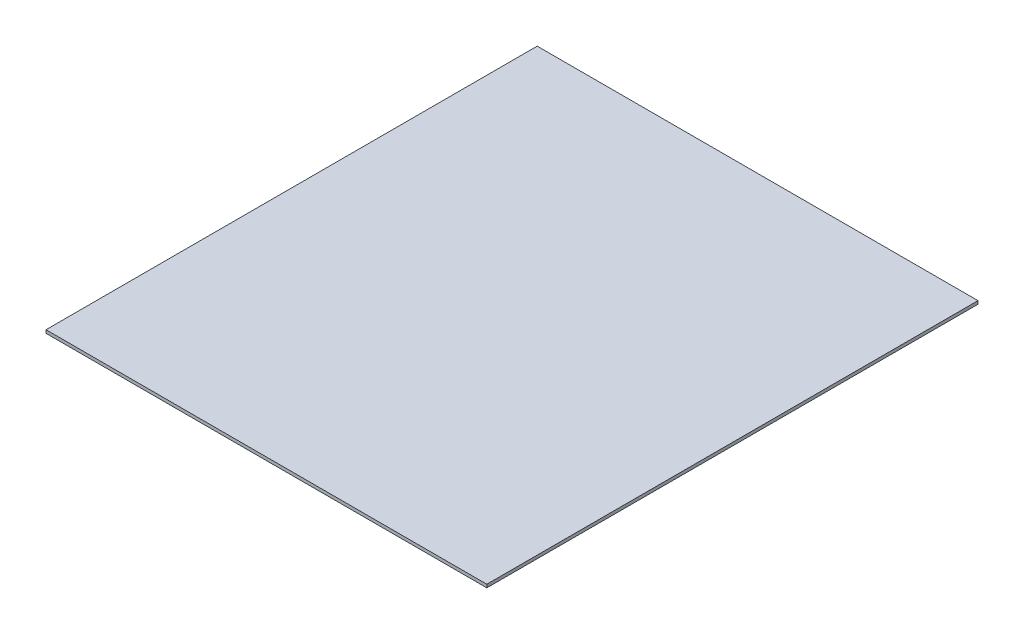
SolidWorks part; units mm, degrees
material "Acrylic (Medium-high impact)"
ref_plane "Front Plane" through (0, 0, 0) normal (0, 0, 1) x (1, 0, 0)
ref_plane "Top Plane" through (0, 0, 0) normal (0, 1, 0) x (1, 0, 0)
ref_plane "Right Plane" through (0, 0, 0) normal (1, 0, 0) x (0, 0, -1)
sketch "Sketch1" plane through (0, 0, 0) normal (0, 1, 0) x (1, 0, 0)
  line L1 (-222.25, -247.65) -> (222.25, -247.65)
  line L2 (-222.25, -247.65) -> (-222.25, 247.65)
  line L3 (-222.25, 247.65) -> (222.25, 247.65)
  line L4 (222.25, -247.65) -> (222.25, 247.65)
  line L5 (-222.25, -247.65) -> (222.25, 247.65) construction
  line L6 (-222.25, 247.65) -> (222.25, -247.65) construction
  point P0 (0, 0)
  dimension "D1" = 495.3
  dimension "D2" = 444.5
extrude "Boss-Extrude1" add sketch "Sketch1" along normal blind 3.175
